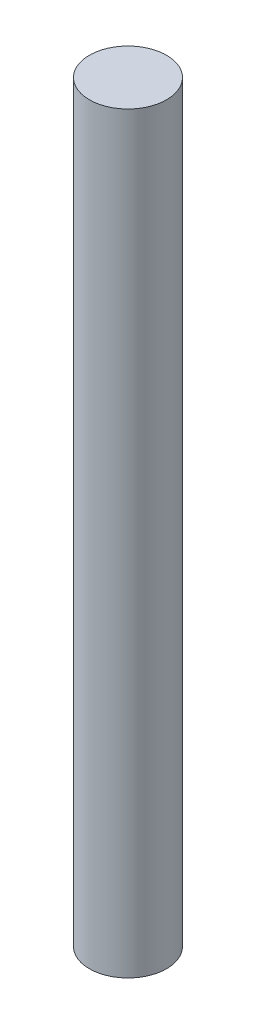
SolidWorks part; units mm, degrees
ref_plane "Front Plane" through (0, 0, 0) normal (0, 0, 1) x (1, 0, 0)
ref_plane "Top Plane" through (0, 0, 0) normal (0, 1, 0) x (1, 0, 0)
ref_plane "Right Plane" through (0, 0, 0) normal (1, 0, 0) x (0, 0, -1)
sketch "Croquis1" plane through (0, 0, 0) normal (0, 1, 0) x (1, 0, 0)
  circle A0 centre (0, 0) radius 4
  dimension "D1" = 8
extrude "Saliente-Extruir1" add sketch "Croquis1" along normal blind 78
